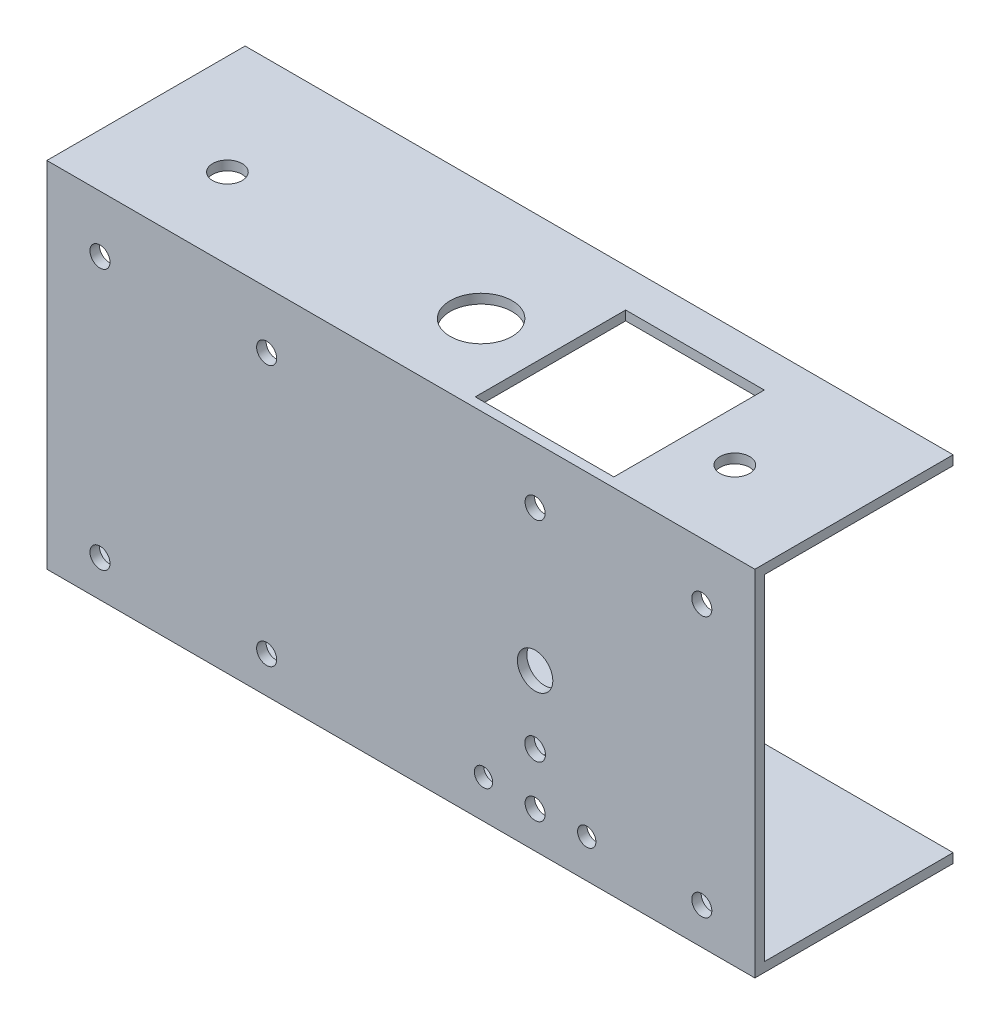
SolidWorks part; units mm, degrees
ref_plane "Front Plane" through (0, 0, 0) normal (0, 0, 1) x (1, 0, 0)
ref_plane "Top Plane" through (0, 0, 0) normal (0, 1, 0) x (1, 0, 0)
ref_plane "Right Plane" through (0, 0, 0) normal (1, 0, 0) x (0, 0, -1)
sketch "Sketch1" plane through (0, 0, 0) normal (0, 1, 0) x (1, 0, 0)
  line L0 (0, -17.6) -> (0, 17.6) construction
  line L13 (34.5, -12) -> (34.5, 13.5)
  line L15 (-60, -12) -> (-60, 20)
  line L16 (-60, 20) -> (60, 20)
  line L17 (60, -12) -> (60, 20)
  line L18 (34.5, 13.5) -> (11, 13.5)
  line L19 (11, 13.5) -> (11, -12)
  line L20 (60, -12) -> (34.5, -12)
  line L21 (11, -12) -> (-60, -12)
  circle A0 centre (0, 0) radius 5.25
  circle A1 centre (-43, 0) radius 2.5
  circle A2 centre (43, 0) radius 2.5
  point P0 (0, 0)
  dimension "D3" = 10.5
  dimension "D4" = 43
  dimension "D5" = 5
  dimension "D1" = 20
  dimension "D2" = 12
  dimension "D6" = 120
  dimension "D7" = 60
  dimension "D9" = 25.5
  dimension "D10" = 23.5
  dimension "D11" = 8.5
other "AlignGroup1"
other "AlignGroup2"
extrude "Boss-Extrude1" add sketch "Sketch1" along normal blind 1.6
sketch "Sketch3" plane through (0, 0, 0) normal (0, -1, 0) x (1, 0, 0)
  line L6 (60, 12) -> (-60, 12)
  line L7 (60, 12) -> (60, 13.6)
  line L8 (60, 13.6) -> (-60, 13.6)
  line L9 (-60, 12) -> (-60, 13.6)
  dimension "D1" = 1.6
extrude "Boss-Extrude3" add sketch "Sketch3" against normal blind 60
ref_plane "Plane1" through (0, 30, 0) normal (0, 1, 0) x (1, 0, 0)
mirror "Mirror1" about plane through (0, 30, 0) normal (0, 1, 0) of "Boss-Extrude1"
sketch "Sketch4" plane through (0, 0, 12) normal (0, 0, 1) x (1, 0, 0)
  line L2 (22.75, 26.5) -> (22.75, 5.2725)
  line L3 (60, 1.6) -> (-60, 1.6) construction
  line L5 (60, 58.4) -> (60, 1.6) construction
  circle A1 centre (22.75, 26.5) radius 3
  circle A5 centre (31.5, 6.5) radius 1.55
  circle A6 centre (14, 6.5) radius 1.55
  circle A7 centre (22.75, 15) radius 1.75
  dimension "D4" = 6
  dimension "D8" = 37.25
  dimension "D13" = 3.5
  dimension "D2" = 3.1
  dimension "D3" = 3.1
  dimension "D5" = 8.75
  dimension "D6" = 8.75
  dimension "D7" = 24.9
  dimension "D12" = 20
  dimension "D14" = 11.5
extrude "Cut-Extrude1" cut sketch "Sketch4" along normal blind 10 contours A1 | A7 L2 | A7 L2 | A5 | A6 region at (23.4927, 15, 12) region at (22.0073, 15, 12) region at (20.6887, 28.5613, 12) region at (31.5, 6.5, 12) region at (14, 6.5, 12)
sketch "Sketch6" plane through (124.2445, 40.7, 12) normal (0, 0, 1) x (1, 0, 0)
  line L0 (-184.2445, -34.5) -> (-64.2445, -34.5)
  line L1 (-101.4945, -14.2) -> (-184.2445, -14.2)
  line L2 (-184.2445, 17.7) -> (-184.2445, -39.1) construction
  line L3 (-129.4945, -59.1) -> (-129.4945, -34.5)
  line L4 (-118.9945, -59.1) -> (-118.9945, -34.5)
  line L5 (-64.2445, 17.7) -> (-64.2445, -39.1) construction
  line L6 (-124.2445, -59.1) -> (-124.2445, -34.5)
  circle A8 centre (-146.9945, -34.5) radius 1.7
  circle A9 centre (-175.2445, -34.5) radius 1.7
  circle A10 centre (-73.2445, -34.5) radius 1.7
  circle A11 centre (-101.4945, -34.5) radius 1.7
  circle A12 centre (-73.2445, 9.7) radius 1.7
  circle A13 centre (-101.4945, 9.7) radius 1.7
  circle A14 centre (-146.9945, 9.7) radius 1.7
  circle A15 centre (-175.2445, 9.7) radius 1.7
  dimension "D3" = 54.75
  dimension "D6" = 44.2
  dimension "D7" = 3.4
  dimension "D8" = 9
  dimension "D9" = 3.4
  dimension "D11" = 3.4
  dimension "D4" = 3.4
  dimension "D5" = 3.4
  dimension "D14" = 3.4
  dimension "D2" = 54.75
  dimension "D10" = 20.3
  dimension "D12" = 17.5
  dimension "D13" = 17.5
extrude "Cut-Extrude2" cut sketch "Sketch6" along normal blind 25 contours A15 | A14 | A13 | A12 | A9 | A8 | A11 | A10 region at (51, 50.4, 12) region at (22.75, 50.4, 12) region at (-22.75, 50.4, 12) region at (-51, 50.4, 12)
sketch "Sketch7" [suppressed] plane through (34.5, 0, 0) normal (-1, 0, 0) x (0, 0, 1)
  line L1 (12, 60) -> (-13.5, 60)
  line L2 (12, 60) -> (12, 58.4)
  line L3 (12, 58.4) -> (-13.5, 58.4)
  line L4 (-13.5, 60) -> (-13.5, 58.4)
extrude "Boss-Extrude4" [suppressed] add sketch "Sketch7" along normal blind 25
